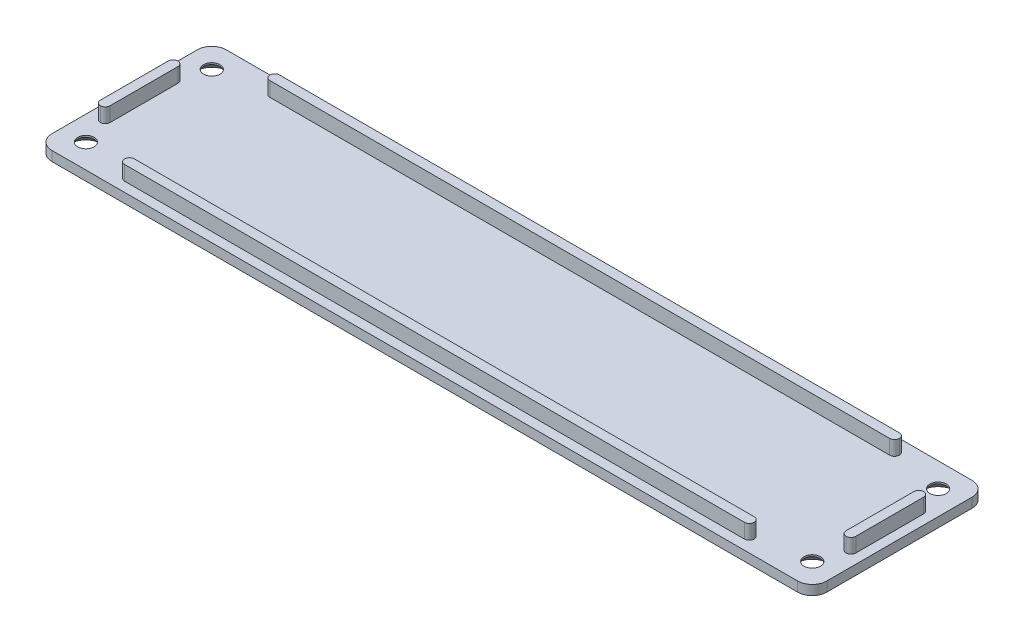
SolidWorks part; units mm, degrees
ref_plane "Front" through (0, 0, 0) normal (0, 0, 1) x (1, 0, 0)
ref_plane "Top" through (0, 0, 0) normal (0, 1, 0) x (1, 0, 0)
ref_plane "Right" through (0, 0, 0) normal (1, 0, 0) x (0, 0, -1)
sketch "Sketch1" plane through (0, 0, 0) normal (0, 1, 0) x (1, 0, 0)
  line L1 (-80, 18) -> (80, 18)
  line L2 (-80, 18) -> (-80, -18)
  line L3 (-80, -18) -> (80, -18)
  line L4 (80, 18) -> (80, -18)
  point P4 (-80, 0)
  point P6 (0, 18)
  dimension "D1" = 160
  dimension "D2" = 36
extrude "Boss-Extrude1" add sketch "Sketch1" along normal blind 2
sketch "Sketch2" plane through (0, 2, 0) normal (0, 1, 0) x (1, 0, 0)
  line L0 (80, 18) -> (-80, 18) construction
  line L1 (-65, 16) -> (65, 16)
  line L2 (-65, 16) -> (-65, 14)
  line L3 (-65, 14) -> (65, 14)
  line L4 (65, 16) -> (65, 14)
  line L5 (76, 8) -> (78, 8)
  line L6 (76, 8) -> (76, -8)
  line L7 (76, -8) -> (78, -8)
  line L8 (78, 8) -> (78, -8)
  line L9 (80, -18) -> (80, 18) construction
  point P8 (76, 0)
  point P10 (0, 14)
  dimension "D1" = 2
  dimension "D2" = 2
  dimension "D3" = 2
  dimension "D4" = 15
  dimension "D5" = 10
extrude "Boss-Extrude2" add sketch "Sketch2" along normal blind 3
ref_axis "Axis1" through (0, -50, 0) along (0, 1, 0)
hole_wizard "CSK for M3 SFHCS1" positions "Sketch5" profile "Sketch7" countersink size "M3" standard "ANSI Metric"
sketch "Sketch5" plane through (0, 0, 0) normal (0, -1, 0) x (-1, 0, 0)
  line L0 (-80, -18) -> (-80, 18) construction
  line L1 (-80, 18) -> (80, 18) construction
  line L2 (80, -18) -> (-80, -18) construction
  point P0 (-75, 13)
  point P2 (-75, -13)
  dimension "D1" = 5
  dimension "D2" = 5
  dimension "D3" = 5
sketch "Sketch7" plane through (75, 0, -13) normal (1, 0, 0) x (0, 0, -1)
  line L0 (0, 0) -> (0, 11.0215)
  line L1 (0, 11.0215) -> (1.7, 10)
  line L2 (1.7, 10) -> (1.7, 1.66)
  line L3 (1.7, 1.66) -> (3.36, 0)
  line L5 (3.36, 0) -> (0, 0)
  line L6 (-1.7, 1.66) -> (-3.36, 0) construction
  line L10 (0, 11.0215) -> (-1.7, 10) construction
  line L11 (0, -6.35) -> (0, 107.95) construction
  dimension "Hole Dia." = 3.4
  dimension "Hole Depth" = 10
  dimension "Near C'Sink Dia." = 6.72
  dimension "Near C'Sink Angle" = 90
  dimension "Drill Angle" = 118
pattern_circular "CirPattern1" count 2 every 180 about axis through (0, -50, 0) along (0, 1, 0) of "Boss-Extrude2", "CSK for M3 SFHCS1"
fillet "Fillet1" radius 3 4 edges at (-80, 1, -18) (80, 1, -18) (80, 1, 18) (-80, 1, 18)
fillet "Fillet2" radius 1 16 edges at (-78, 3.5, -8) (-78, 3.5, 8) (-76, 3.5, 8) (-76, 3.5, -8) (-65, 3.5, 14) (-65, 3.5, 16) (65, 3.5, 16) (65, 3.5, 14) (78, 3.5, 8) (78, 3.5, -8) (76, 3.5, -8) (76, 3.5, 8) (65, 3.5, -14) (65, 3.5, -16) (-65, 3.5, -16) (-65, 3.5, -14)
